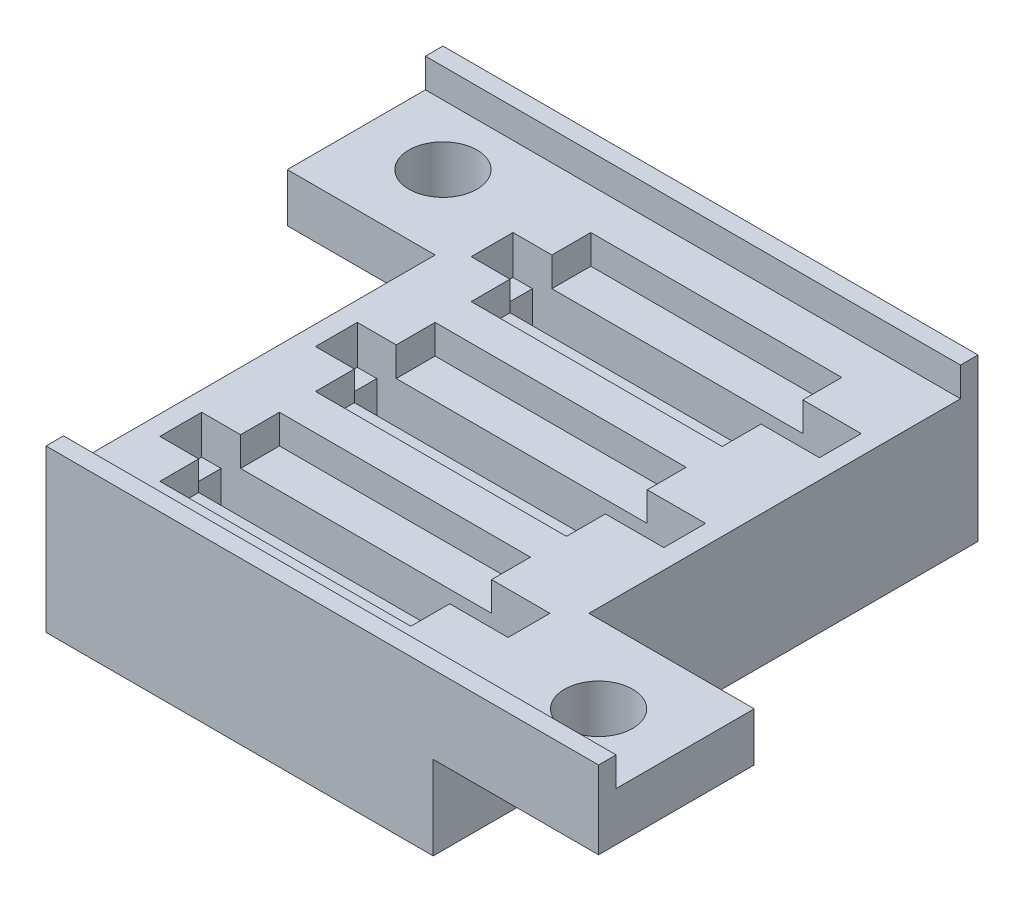
SolidWorks part; units mm, degrees
ref_plane "Front Plane" through (0, 0, 0) normal (0, 0, 1) x (1, 0, 0)
ref_plane "Top Plane" through (0, 0, 0) normal (0, 1, 0) x (1, 0, 0)
ref_plane "Right Plane" through (0, 0, 0) normal (1, 0, 0) x (0, 0, -1)
sketch "Sketch1" plane through (0, 0, 0) normal (0, 1, 0) x (1, 0, 0)
  line L0 (15.9, 9.075) -> (0, 9.075) construction
  line L1 (0, 0) -> (15.9, 0)
  line L2 (0, 0) -> (0, 2.15)
  line L3 (0, 2.15) -> (15.9, 2.15)
  line L4 (15.9, 0) -> (15.9, 2.15)
  line L5 (0, 8) -> (15.9, 8)
  line L6 (0, 8) -> (0, 10.15)
  line L7 (0, 10.15) -> (15.9, 10.15)
  line L8 (15.9, 8) -> (15.9, 10.15)
  line L9 (0, 16) -> (15.9, 16)
  line L10 (0, 16) -> (0, 18.15)
  line L11 (0, 18.15) -> (15.9, 18.15)
  line L12 (15.9, 16) -> (15.9, 18.15)
  line L13 (7.95, 28.0047) -> (7.95, -5.2427) construction
  line L14 (-2, 15.15) -> (-2, -4.85)
  line L35 (26.4, -4.85) -> (-2, -4.85)
  line L36 (26.4, -4.85) -> (26.4, 3.15)
  line L37 (26.4, 3.15) -> (17.9, 3.15)
  line L39 (-9.6, 23.15) -> (17.9, 23.15)
  line L40 (-9.6, 23.15) -> (-9.6, 15.15)
  line L41 (-9.6, 15.15) -> (-2, 15.15)
  line L43 (17.9, 23.15) -> (17.9, 3.15)
  circle A2 centre (-5.6, 19.15) radius 1.75
  circle A3 centre (22.4, -0.85) radius 1.75
  point P25 (7.95, 10.15)
  dimension "D6" = 6.5
  dimension "D7" = 1
  dimension "D13" = 4
  dimension "D8" = 3.5
  dimension "D1" = 2.15
  dimension "D2" = 15.9
  dimension "D3" = 8
  dimension "D4" = 16
  dimension "D5" = 21.5
  dimension "D9" = 2
  dimension "D10" = 2
  dimension "D11" = 28
  dimension "D12" = 3
  dimension "D14" = 4
  dimension "D15" = 4
  dimension "D16" = 4
  dimension "D17" = 4
  dimension "D18" = 4
  dimension "D19" = 19.9
extrude "Base" add sketch "Sketch1" along normal blind 2.5 contours L41 | L41 A3 | L37 A2 | L12 L9 L10 L11 L8 L5 L6 L7 L4 L1 L2 L3 region at (-5.8, 0, -15.6061)
sketch "Sketch3" plane through (0, 2.5, 0) normal (0, 1, 0) x (1, 0, 0)
  line L0 (15.9, 0) -> (15.9, 2.15) construction
  line L1 (0, 0) -> (0, 2.15) construction
  line L2 (15.9, 8) -> (15.9, 10.15) construction
  line L3 (0, 8) -> (0, 10.15) construction
  line L4 (15.9, 16) -> (15.9, 18.15) construction
  line L5 (0, 16) -> (0, 18.15) construction
  line L18 (15.9, 0) -> (15.9, 2.15) construction
  line L19 (0, 0) -> (0, 2.15) construction
  line L20 (0, 8) -> (0, 10.15) construction
  line L21 (15.9, 8) -> (15.9, 10.15) construction
  line L22 (15.9, 16) -> (15.9, 18.15) construction
  line L23 (0, 16) -> (0, 18.15) construction
  line L24 (16.9, 16) -> (16.9, 18.15)
  line L25 (16.9, 8) -> (16.9, 10.15)
  line L26 (16.9, 0) -> (16.9, 2.15)
  line L27 (-1, 16) -> (-1, 18.15)
  line L28 (-1, 8) -> (-1, 10.15)
  line L29 (-1, 0) -> (-1, 2.15)
  line L30 (-1, 18.15) -> (16.9, 18.15)
  line L31 (-1, 16) -> (16.9, 16)
  line L32 (-1, 10.15) -> (16.9, 10.15)
  line L33 (-1, 8) -> (16.9, 8)
  line L34 (-1, 2.15) -> (16.9, 2.15)
  line L35 (-1, 0) -> (16.9, 0)
  dimension "D1" = 1
  dimension "D2" = 1
extrude "Cut-Extrude1" cut sketch "Sketch3" against normal blind 2
sketch "Sketch4" plane through (0, 0, 0) normal (0, -1, 0) x (1, 0, 0)
  line L1 (-2, 4.85) -> (17.9, 4.85)
  line L2 (-2, 4.85) -> (-2, -23.15)
  line L3 (-2, -23.15) -> (17.9, -23.15)
  line L4 (17.9, 4.85) -> (17.9, -23.15)
  line L8 (15.9, -18.15) -> (15.9, -16)
  line L9 (0, -18.15) -> (15.9, -18.15)
  line L10 (0, -16) -> (0, -18.15)
  line L11 (15.9, -16) -> (0, -16)
  line L12 (15.9, -18.15) -> (15.9, -16)
  line L13 (0, -18.15) -> (15.9, -18.15)
  line L14 (0, -16) -> (0, -18.15)
  line L15 (15.9, -16) -> (0, -16)
  line L16 (15.9, -10.15) -> (15.9, -8)
  line L17 (0, -10.15) -> (15.9, -10.15)
  line L18 (0, -8) -> (0, -10.15)
  line L19 (15.9, -8) -> (0, -8)
  line L20 (15.9, -10.15) -> (15.9, -8)
  line L21 (0, -10.15) -> (15.9, -10.15)
  line L22 (0, -8) -> (0, -10.15)
  line L23 (15.9, -8) -> (0, -8)
  line L24 (15.9, -2.15) -> (15.9, 0)
  line L25 (0, -2.15) -> (15.9, -2.15)
  line L26 (0, 0) -> (0, -2.15)
  line L27 (15.9, 0) -> (0, 0)
  line L28 (15.9, -2.15) -> (15.9, 0)
  line L29 (0, -2.15) -> (15.9, -2.15)
  line L30 (0, 0) -> (0, -2.15)
  line L31 (15.9, 0) -> (0, 0)
  dimension "D1" = 0
  dimension "D2" = 0
  dimension "D3" = 0
extrude "Boss-Extrude1" add sketch "Sketch4" along normal blind 4.3
sketch "Sketch5" plane through (0, 2.5, 0) normal (0, 1, 0) x (1, 0, 0)
  line L0 (-1, 18.15) -> (16.9, 18.15) construction
  line L1 (1, 20.15) -> (13.9, 20.15)
  line L2 (1, 20.15) -> (1, 14)
  line L3 (1, 14) -> (13.9, 14)
  line L4 (13.9, 20.15) -> (13.9, 14)
  line L5 (1, 12.15) -> (13.9, 12.15)
  line L6 (1, 12.15) -> (1, 6)
  line L7 (1, 6) -> (13.9, 6)
  line L8 (13.9, 12.15) -> (13.9, 6)
  line L9 (1, 4.15) -> (13.9, 4.15)
  line L10 (1, 4.15) -> (1, -2)
  line L11 (1, -2) -> (13.9, -2)
  line L12 (13.9, 4.15) -> (13.9, -2)
  line L13 (-1, 16) -> (16.9, 16) construction
  line L14 (-1, 10.15) -> (16.9, 10.15) construction
  line L15 (-1, 8) -> (16.9, 8) construction
  line L16 (-1, 2.15) -> (16.9, 2.15) construction
  line L17 (-1, 0) -> (16.9, 0) construction
  line L18 (15.9, 16) -> (15.9, 18.15) construction
  line L19 (-1, 18.15) -> (-1, 16) construction
  point P26 (15.9, 17.075)
  dimension "D1" = 2
  dimension "D2" = 2
  dimension "D3" = 2
  dimension "D4" = 2
  dimension "D5" = 2
  dimension "D6" = 2
  dimension "D7" = 2
  dimension "D8" = 2
extrude "Cut-Extrude2" cut sketch "Sketch5" against normal blind 1.5
sketch "Sketch6" plane through (0, 2.5, 0) normal (0, 1, 0) x (1, 0, 0)
  line L0 (17.9, 23.15) -> (17.9, 3.15) construction
  line L1 (-9.6, 23.15) -> (17.9, 23.15)
  line L2 (-9.6, 23.15) -> (-9.6, 22.25)
  line L3 (-9.6, 22.25) -> (17.9, 22.25)
  line L4 (17.9, 23.15) -> (17.9, 22.25)
  line L5 (26.4, -4.85) -> (26.4, 3.15) construction
  line L6 (-2, -4.85) -> (26.4, -4.85)
  line L7 (-2, -4.85) -> (-2, -3.95)
  line L8 (-2, -3.95) -> (26.4, -3.95)
  line L9 (26.4, -4.85) -> (26.4, -3.95)
  dimension "D1" = 0.9
  dimension "D2" = 0.9
extrude "Boss-Extrude2" add sketch "Sketch6" along normal blind 1.5 contours L3 L4 L1 L2
extrude "Boss-Extrude3" add sketch "Sketch6<3>" along normal blind 1.5
sketch "Sketch6<3>" plane through (0, 2.5, 0) normal (0, 1, 0) x (1, 0, 0) same geometry as "Sketch6"
